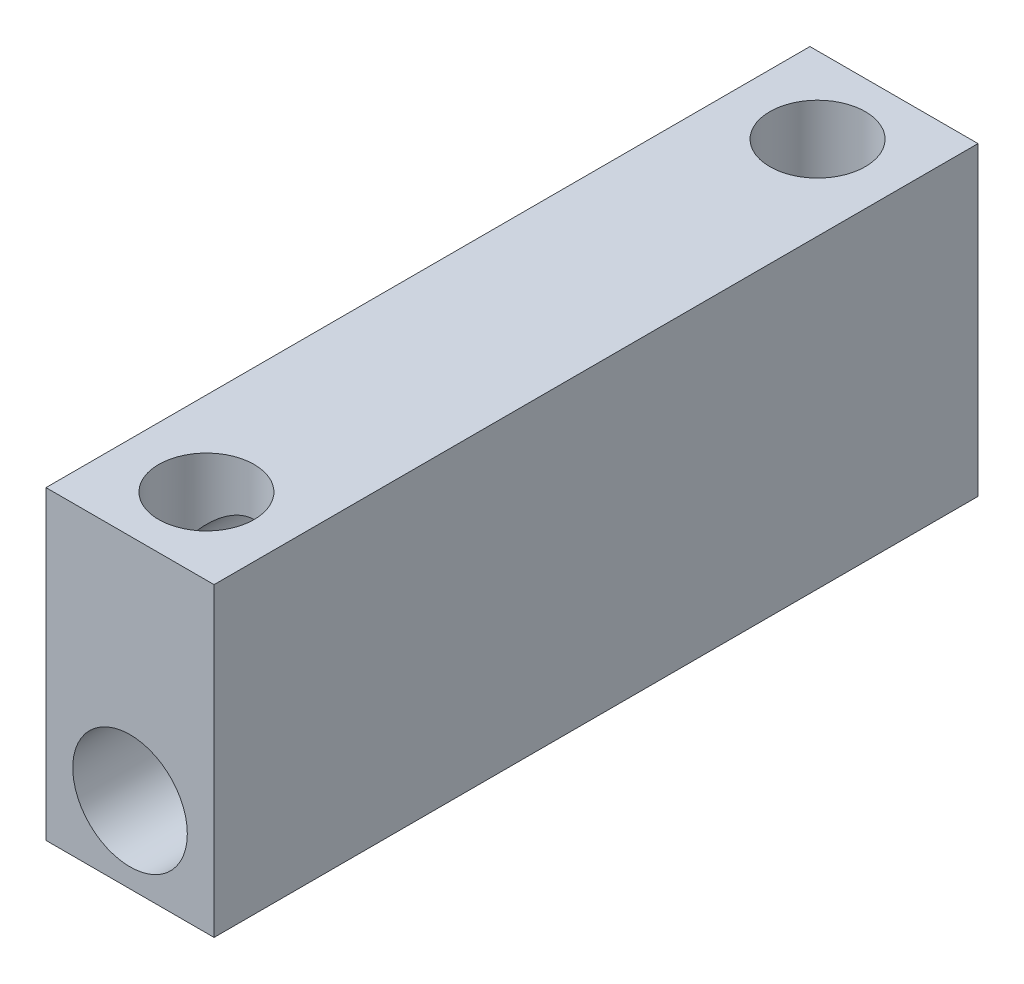
SolidWorks part; units mm, degrees
ref_plane "Front Plane" through (0, 0, 0) normal (0, 0, 1) x (1, 0, 0)
ref_plane "Top Plane" through (0, 0, 0) normal (0, 1, 0) x (1, 0, 0)
ref_plane "Right Plane" through (0, 0, 0) normal (1, 0, 0) x (0, 0, -1)
sketch "Sketch1" plane through (0, 0, 0) normal (1, 0, 0) x (0, 0, -1)
  line L1 (127, 50.8) -> (-127, 50.8)
  line L2 (127, 50.8) -> (127, -50.8)
  line L3 (127, -50.8) -> (-127, -50.8)
  line L4 (-127, 50.8) -> (-127, -50.8)
  line L5 (127, 50.8) -> (-127, -50.8) construction
  line L6 (127, -50.8) -> (-127, 50.8) construction
  point P0 (0, 0)
  dimension "D1" = 254
  dimension "D2" = 101.6
extrude "Boss-Extrude1" add sketch "Sketch1" along normal mid plane 55.88
sketch "Sketch2" plane through (0, 50.8, 0) normal (0, 1, 0) x (1, 0, 0)
  line L0 (-39.0589, 0) -> (56.365, 0) construction
  circle A0 centre (0, 101.6) radius 15.875
  circle A1 centre (0, -101.6) radius 15.875
  dimension "D1" = 31.75
  dimension "D2" = 101.6
extrude "Cut-Extrude1" cut sketch "Sketch2" against normal blind 50.8
sketch "Sketch3" plane through (0, 0, 0) normal (0, 0, 1) x (1, 0, 0)
  line L1 (27.94, 50.8) -> (-27.94, 50.8) construction
  circle A0 centre (0, 19.05) radius 15.875
  dimension "D1" = 31.75
  dimension "D2" = 31.75
extrude "Cut-Extrude2" cut sketch "Sketch3" against normal up to surface and the other way up to surface up to face at (0, 0, -85.725) other way up to face at (0, 0, 85.725)
sketch "Sketch4" plane through (0, 0, 127) normal (0, 0, 1) x (1, 0, 0)
  circle A0 centre (0, -25.4) radius 19.05
  dimension "D1" = 38.1
  dimension "D2" = 25.4
extrude "Cut-Extrude3" cut sketch "Sketch4" against normal offset from surface (241.3 mm away) 12.7 up to face at (0, 0, -127)
sketch "Sketch5" plane through (-27.94, 0, 0) normal (-1, 0, 0) x (0, 0, 1)
  text T0 "TforDesign.com"
extrude "Cut-Extrude4" cut sketch "Sketch5" against normal blind 0.0254
